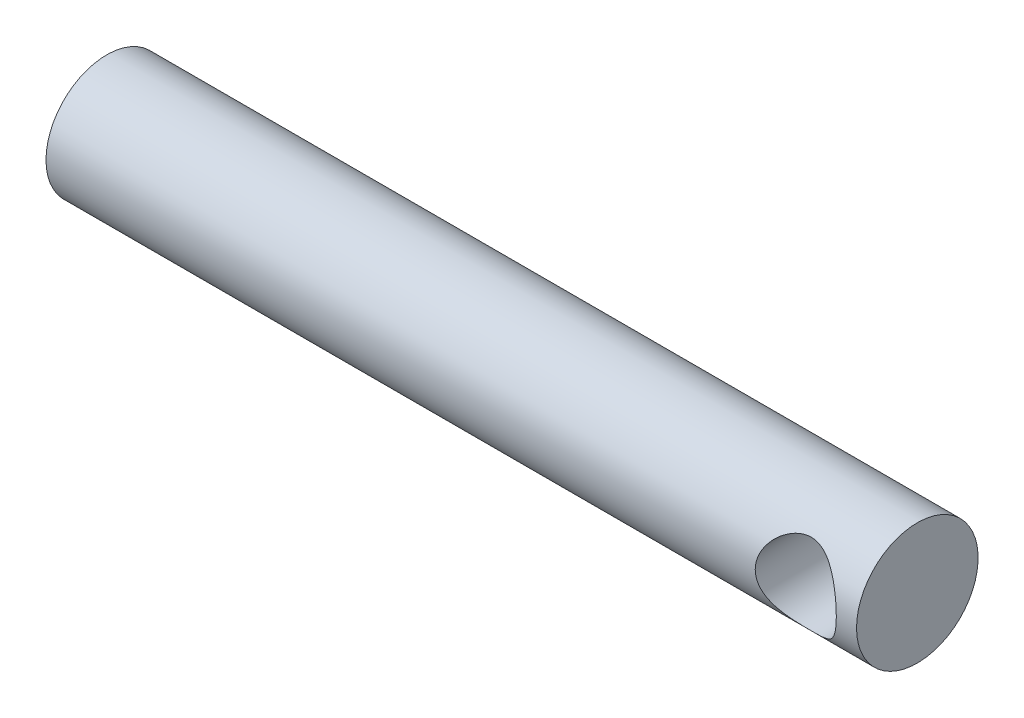
SolidWorks part; units mm, degrees
ref_plane "Front Plane" through (0, 0, 0) normal (0, 0, 1) x (1, 0, 0)
ref_plane "Top Plane" through (0, 0, 0) normal (0, 1, 0) x (1, 0, 0)
ref_plane "Right Plane" through (0, 0, 0) normal (1, 0, 0) x (0, 0, -1)
sketch "Sketch1" plane through (0, 0, 0) normal (0, 0, 1) x (1, 0, 0)
  line L0 (-20, 0) -> (20, 0) construction
  line L1 (-20, 0) -> (20, 0)
  line L2 (-20, 0) -> (-20, 3)
  line L3 (-20, 3) -> (20, 3)
  line L4 (20, 0) -> (20, 3)
  line L5 (-20, -3) -> (20, 3) construction
  line L6 (-20, 3) -> (20, -3) construction
  point P0 (0, 0)
  dimension "D1" = 6
  dimension "D2" = 40
revolve "Revolve1" add sketch "Sketch1" angle 360 about L1
sketch "Sketch2" plane through (0, 0, 0) normal (0, 0, 1) x (1, 0, 0)
  line L0 (20, -3) -> (20, 3) construction
  circle A0 centre (17, 0) radius 2
  dimension "D1" = 4
  dimension "D2" = 3
extrude "Cut-Extrude1" cut sketch "Sketch2" against normal blind 10 and the other way blind 10
